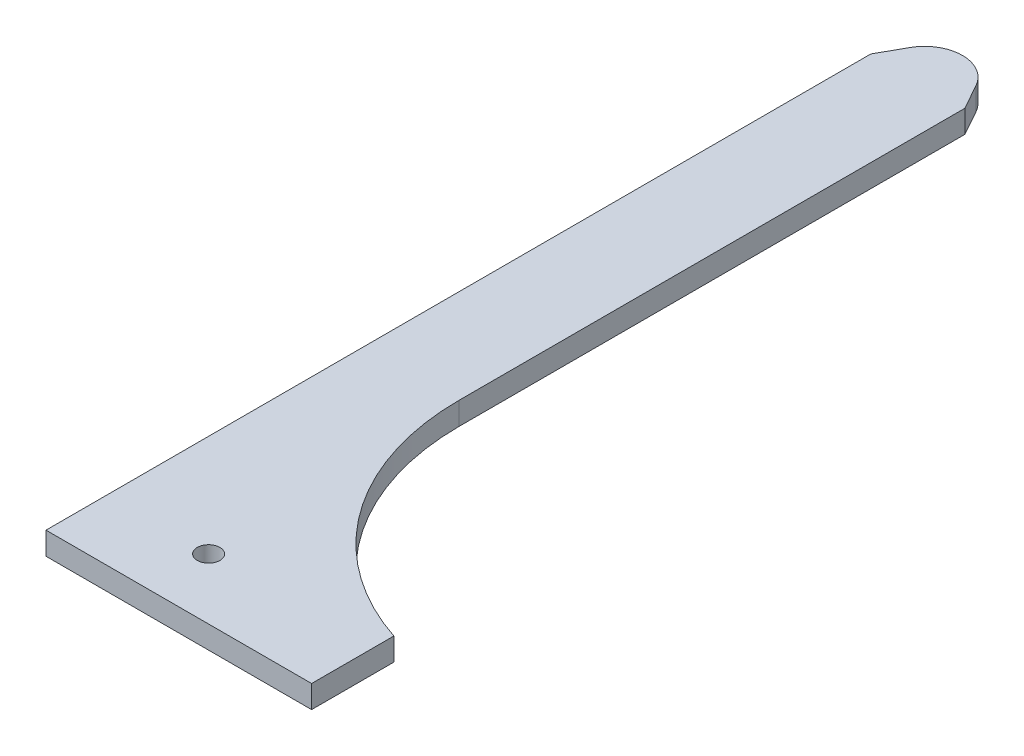
SolidWorks part; units mm, degrees
ref_plane "前视基准面" through (0, 0, 0) normal (0, 0, 1) x (1, 0, 0)
ref_plane "上视基准面" through (0, 0, 0) normal (0, 1, 0) x (1, 0, 0)
ref_plane "右视基准面" through (0, 0, 0) normal (1, 0, 0) x (0, 0, -1)
other "Configuration Table"
sketch "草图1" plane through (0, 0, 0) normal (0, 1, 0) x (1, 0, 0)
  line L0 (0, 48) -> (0, -48)
  line L1 (0, -48) -> (0, -107.8621)
  line L6 (-45.46, -107.8621) -> (25.79, -107.8621)
  line L11 (-45.46, -107.8621) -> (-45.46, -32.8621)
  line L12 (25.79, -107.8621) -> (25.79, -32.8621)
  line L13 (-45.46, -32.8621) -> (25.79, -32.8621)
  line L14 (25.79, -42.2621) -> (-45.46, -42.2621)
  line L15 (-45.46, -32.8621) -> (5.01, -32.8621)
  line L16 (-45.46, -32.8621) -> (-45.46, 27.8779)
  line L17 (-45.46, 27.8779) -> (5.01, 27.8779)
  line L18 (5.01, -32.8621) -> (5.01, 27.8779)
  line L19 (-10.2743, -42.2621) -> (-10.2743, -31.3598)
  line L20 (-31.96, -42.2621) -> (-31.96, -34.2221) construction
  line L21 (-31.96, -34.2221) -> (-45.46, -34.2221) construction
  line L22 (0, 0) -> (-48, 0) construction
  line L23 (-39.23, 67) -> (-39.23, 78.1855) construction
  line L24 (-33, 0) -> (-45.46, 0)
  line L25 (-33, 0) -> (-33, 67)
  line L26 (-33, 67) -> (-45.46, 67)
  line L27 (-45.46, 0) -> (-45.46, 67)
  line L28 (-39.23, 78.1855) -> (-45.46, 67)
  line L29 (-39.23, 78.1855) -> (-33, 67)
  circle A0 centre (0, 0) radius 33
  circle A1 centre (0, 0) radius 48
  circle A2 centre (-31.96, -34.2221) radius 1.5
  dimension "D1" = 66
  dimension "D2" = 96
  dimension "D11" = 3
  dimension "D3" = 71.25
  dimension "D4" = 25.79
  dimension "D5" = 75
  dimension "D6" = 60.74
  dimension "D7" = 50.47
  dimension "D8" = 9.4
  dimension "D9" = 13.5
  dimension "D10" = 8.04
  dimension "D12" = 67
extrude "凸台-拉伸1" add sketch "草图1" along normal blind 3 contours A1 L25 L26 L27 L17 | L25 A1 L17 | A2 L15 L19 A0 L17 L25 L24 L16 A1 | L17 A1 L16 L24 L25 | A1 L17 L27 | A2 A1 L14 L19 L15 | A2 A1 L13 L11 L14 | A1 L16 L13 | A2 L15 A1 | L29 L28 L26 region at (-39.431, 0, -48.2723) region at (-35.0908, 0, -30.2789) region at (-38.7567, 0, -12.812) region at (-39.23, 0, -70.7285) region at (-43.4525, 0, -23.9935) region at (-33.5336, 0, 18.5001) region at (-42.2348, 0, 27.5644) region at (-19.6707, 0, 37.2142) region at (-37.1361, 0, 38.1643) region at (-33.8099, 0, 33.3402)
fillet "圆角4" radius 5 1 edges at (-39.23, 1.5, -78.1855)
